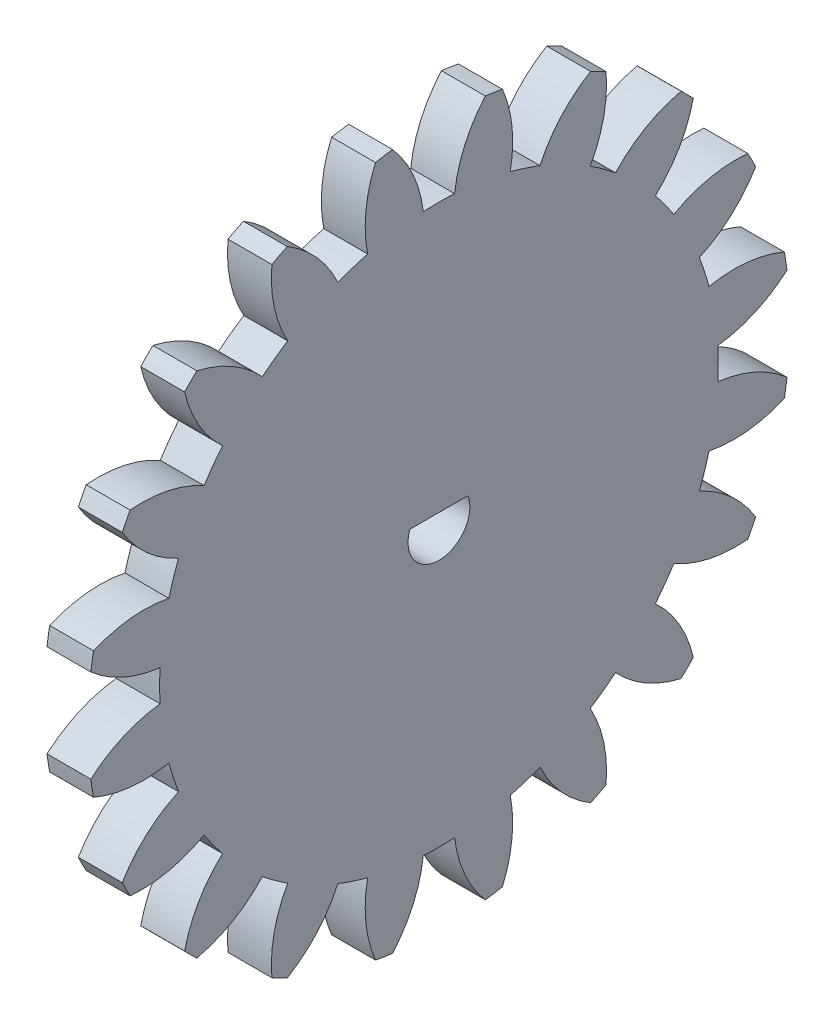
SolidWorks part; units mm, degrees
ref_plane "Plane1" through (0, 0, 0) normal (0, 0, 1) x (1, 0, 0)
ref_plane "Plane2" through (0, 0, 0) normal (0, 1, 0) x (1, 0, 0)
ref_plane "Plane3" through (0, 0, 0) normal (1, 0, 0) x (0, 0, -1)
sketch "HoldingSke" plane through (0, 0, 0) normal (0, 1, 0) x (1, 0, 0)
  line L0 (0, 0) -> (0.2349, -0.0855)
  line L1 (-15, 0) -> (100, 0) construction
  line L2 (0, 0) -> (-2.1039, 2.3779)
  line L3 (0, 0) -> (-11.863, 4.5341)
  line L4 (0, 0) -> (8.1152, 2.9537)
  line L5 (0, 0) -> (-46.8476, -17.4728)
  line L6 (0, 0) -> (-4.5593, -3.0762)
  line L7 (-2.1039, 2.3779) -> (8.6586, 51.2059)
  line L8 (-76.2, 54.61) -> (-76.1, 54.61)
  line L9 (-71.009, 38.7566) -> (-53.1078, 45.2721)
  line L10 (-76.2, 71.12) -> (104.1128, 71.12)
  line L11 (0, 0) -> (-5.5, 0)
  line L12 (-76.2, 101.6) -> (-76.073, 101.6)
  line L13 (24.9733, 27.94) -> (52.9518, 28.4284)
  line L14 (24.9733, 27.94) -> (24.9743, 27.94)
  line L15 (24.9733, 27.94) -> (100.4006, 29.5858)
  line L16 (-63.627, -4) -> (-12.827, -4)
  circle A0 centre (0, 0) radius 0.5
  circle A1 centre (0, 0) radius 34.999
  circle A2 centre (0, 0) radius 37.5
  circle A3 centre (0, 0) radius 0.5
  dimension "MHD" = 69.998
  dimension "Hub_dia" = 75
  dimension "Bore" = 1
  dimension "MBD" = 1
  dimension "Num_teeth" = 20
  dimension "Pitch" = 0.25
  dimension "Overall_len" = 50
  dimension "Show_teeth" = 20
  dimension "Thickness" = 5.5
  dimension "OAL" = 50.0001
  dimension "T_dim" = 0.1
  dimension "Ap" = 20
  dimension "H" = 19.05
  dimension "Pitch_radius" = 180.3128
  dimension "Width" = 5.5
  dimension "Backlash" = 0.127
  dimension "Addendum_fac" = 1
  dimension "Dedendum_fac" = 1.25
  dimension "Clearance_fac" = 0.25
  dimension "Dedendum_add" = 0.001
  dimension "Module" = 4
sketch "BasProSke" plane through (0, 0, 0) normal (0, 1, 0) x (1, 0, 0)
  line L0 (-10, 0) -> (60, 0) construction
  line L1 (0, 0) -> (0, 44)
  line L2 (0, 0) -> (5.5, 0)
  line L3 (5.5, 0) -> (5.5, 44)
  line L4 (5.5, 44) -> (0, 44)
  dimension "Thickness" = 5.5
  dimension "Diameter" = 88
revolve "Base-Revolve" add sketch "BasProSke" angle 360 about L0
sketch "TooCutSke" plane through (0, 0, 0) normal (1, 0, 0) x (0, 0, -1)
  line L1 (0, 0) -> (0, 107) construction
  line L2 (0, 0) -> (-3.3605, 39.8586) construction
  line L3 (0, 0) -> (-12.4815, 78.8048) construction
  line L4 (-3.3605, 39.8586) -> (-6.2407, 39.4024) construction
  arc A0 (1.9617, 34.944) -> (-1.9617, 34.944) centre (0, 0) ccw
  arc A1 (5.8321, 43.6374) -> (-5.8321, 43.6374) centre (0, 0) ccw
  circle A2 centre (0, 0) radius 40 construction
  circle A3 centre (0, 0) radius 37.5877 construction
  arc A4 (-1.9617, 34.944) -> (-5.8321, 43.6374) centre (-17.8525, 33.0775) ccw
  arc A5 (5.8321, 43.6374) -> (1.9617, 34.944) centre (17.8525, 33.0775) ccw
  dimension "Root_dia" = 69.998
  dimension "Overcut_dia" = 88.0508
  dimension "Pitch_dia" = 80
  dimension "Base_dia" = 75.1754
  dimension "Flank_rad" = 16
  dimension "Half_ang" = 9
  dimension "Half_CT" = 2.9161
extrude "ToothCut" cut sketch "TooCutSke" along normal through all
fillet "Breaks" [suppressed] radius 0.08 tangent propagation no
fillet "RootFillets" [suppressed] radius 1.001
pattern_circular "TeethCuts" count 20 every 18 about axis through (-10, 0, 0) along (1, 0, 0) of "ToothCut", "RootFillets", "Breaks"
sketch "HubNeaOneSke" plane through (0, 0, 0) normal (-1, 0, 0) x (0, 0, 1)
  circle A0 centre (0, 0) radius 34.999
  dimension "Diameter" = 69.998
extrude "HubNearOne" [suppressed] add sketch "HubNeaOneSke" along normal blind 44.5001
sketch "HubNeaBotSke" plane through (0, 0, 0) normal (-1, 0, 0) x (0, 0, 1)
  circle A0 centre (0, 0) radius 34.999
  dimension "Diameter" = 69.998
extrude "HubNearBoth" [suppressed] add sketch "HubNeaBotSke" along normal blind 22.25
ref_plane "FarPln" through (5.5, 0, 0) normal (1, 0, 0) x (0, 0, -1)
sketch "HubFarSke" plane through (5.5, 0, 0) normal (1, 0, 0) x (0, 0, -1)
  circle A0 centre (0, 0) radius 34.999
  dimension "Diameter" = 69.998
extrude "HubFar" [suppressed] add sketch "HubFarSke" along normal blind 22.25
sketch "BorSke" plane through (0, 0, 0) normal (1, 0, 0) x (0, 0, -1)
  circle A0 centre (0, 0) radius 0.5
  dimension "Diameter" = 1
extrude "Bore" cut sketch "BorSke" along normal mid plane 100.0001
sketch "KeySke" plane through (0, 0, 0) normal (1, 0, 0) x (0, 0, -1)
  line L0 (-0.05, 0) -> (-0.05, 0.6)
  line L1 (-0.05, 0.6) -> (0.05, 0.6)
  line L2 (0.05, 0.6) -> (0.05, 0)
  line L3 (0, 0) -> (0, 34) construction
  line L4 (-0.05, 0) -> (0.05, 0)
  dimension "Offset" = 0.6
  dimension "Width" = 0.1
extrude "Keyway" [suppressed] cut sketch "KeySke" along normal mid plane 100.0001
pattern_circular "Keyway2" [suppressed] count 2 every 90 about axis through (-10, 0, 0) along (1, 0, 0)
sketch "Croquis1" plane through (5.5, 0, 0) normal (1, 0, 0) x (0, 0, -1)
  line L1 (0, -3.875) -> (0, 1.325) construction
  line L2 (0, 1.325) -> (3.6414, 1.325)
  line L3 (0, 1.325) -> (-3.6414, 1.325)
  arc A0 (-3.875, 0) -> (3.875, 0) centre (0, 0) ccw
  arc A1 (3.875, 0) -> (3.6414, 1.325) centre (0, 0) ccw
  arc A2 (-3.6414, 1.325) -> (-3.875, 0) centre (0, 0) ccw
  dimension "D1" = 7.75
  dimension "D2" = 5.2
extrude "Cortar-Extruir1" cut sketch "Croquis1" against normal blind 5.5
sketch "Croquis2" plane through (5.5, 0, 0) normal (1, 0, 0) x (0, 0, -1)
  line L0 (-0.5, 0) -> (0.5, 0)
  arc A0 (0.5, 0) -> (-0.5, 0) centre (0, 0) ccw
extrude "Saliente-Extruir1" [suppressed] add sketch "Croquis2" against normal blind 5.5
equation "' \"Module@HoldingSke\" = 6.35"
equation "' \"Num_teeth@HoldingSke\" = 12"
equation "' \"Ap@HoldingSke\" =  20"
equation "' \"Ap@HoldingSke\" = 20"
equation "' \"Width@HoldingSke\" = 0.5 * 25.4"
equation "' \"Hub_dia@HoldingSke\"= 1 * 25.4"
equation "' \"Hub_dia@HoldingSke\" = 1 * 25.4"
equation "' \"Overall_len@HoldingSke\" = 1.0 * 25.4"
equation "' \"Bore@HoldingSke\" = 0.75 * 25.4"
equation "' \"T_dim@HoldingSke\" = 0.1 * 25.4"
equation "' \"Width@KeySke\" = 0.25 * 25.4"
equation "' \"Show_teeth@HoldingSke\" = 13"
equation "' \"Backlash@HoldingSke\" = 0.009 * 25.4"
equation "' \"Addendum_fac@HoldingSke\" = 1.0"
equation "' \"Dedendum_fac@HoldingSke\" = 1.25"
equation "' \"Dedendum_add@HoldingSke\" = 0.00005 * 25.4"
equation "' \"Clearance_fac@HoldingSke\" = 0.25"
equation "\"Pitch@HoldingSke\" = 1 / \"Module@HoldingSke\""
equation "\"Overcut_dia@TooCutSke\" = (\"Num_teeth@HoldingSke\" + 2 * \"Addendum_fac@HoldingSke\") / \"Pitch@HoldingSke\" + 0.002 * 25.4"
equation "\"Pitch_dia@TooCutSke\" = \"Num_teeth@HoldingSke\" / \"Pitch@HoldingSke\""
equation "\"Base_dia@TooCutSke\" = \"Num_teeth@HoldingSke\" / \"Pitch@HoldingSke\" * cos((\"Ap@HoldingSke\"  * 3.14159265 / 180))"
equation "\"Root_dia@TooCutSke\" = (\"Num_teeth@HoldingSke\" + 2) / \"Pitch@HoldingSke\" - 2 * (\"Addendum_fac@HoldingSke\" + \"Dedendum_fac@HoldingSke\") / \"Pitch@HoldingSke\" - \"Dedendum_add@HoldingSke\" * 2"
equation "\"Half_ang@TooCutSke\" = 180 / \"Num_teeth@HoldingSke\""
equation "\"Half_CT@TooCutSke\" = \"Num_teeth@HoldingSke\" / \"Pitch@HoldingSke\" * sin((3.14159265 / 2 / \"Num_teeth@HoldingSke\")) / 2 - 7 * \"Backlash@HoldingSke\" / 4"
equation "\"Flank_rad@TooCutSke\" = \"Num_teeth@HoldingSke\" / \"Pitch@HoldingSke\" / 5"
equation "\"Radius@RootFillets\" = \"Clearance_fac@HoldingSke\" / \"Pitch@HoldingSke\" + \"Dedendum_add@HoldingSke\""
equation "\"Break_rad@Breaks\" = 0.02 / \"Pitch@HoldingSke\""
equation "\"Thickness@HoldingSke\" = \"Width@HoldingSke\""
equation "\"OAL@HoldingSke\" = \"Thickness@HoldingSke\""
equation "\"MHD@HoldingSke\" = (\"Num_teeth@HoldingSke\" + 2) / \"Pitch@HoldingSke\" - 2 * (\"Addendum_fac@HoldingSke\" + \"Dedendum_fac@HoldingSke\")  / \"Pitch@HoldingSke\" - \"Dedendum_add@HoldingSke\" * 2"
equation "\"MBD@HoldingSke\" = (\"Num_teeth@HoldingSke\" + 2) / \"Pitch@HoldingSke\" - 2 * (\"Addendum_fac@HoldingSke\" + \"Dedendum_fac@HoldingSke\")  / \"Pitch@HoldingSke\" - \"Dedendum_add@HoldingSke\" * 2 - 0.002 * 25.4"
equation "\"MHD@HoldingSke\" = ((sgn( \"MHD@HoldingSke\" - \"Hub_dia@HoldingSke\" )-1)*( \"MHD@HoldingSke\" - \"Hub_dia@HoldingSke\" ))/-2+ \"Hub_dia@HoldingSke\""
equation "\"MBD@HoldingSke\" = ((sgn( \"MBD@HoldingSke\" - \"Bore@HoldingSke\" )-1)*( \"MBD@HoldingSke\" - \"Bore@HoldingSke\" ))/-2+ \"Bore@HoldingSke\""
equation "\"OAL@HoldingSke\" = ((sgn( \"OAL@HoldingSke\" - \"Overall_len@HoldingSke\" )+1)*( \"OAL@HoldingSke\" - \"Overall_len@HoldingSke\" ))/2 + \"Overall_len@HoldingSke\" + 0.000002 * 25.4"
equation "\"Num_teeth@TeethCuts\" = int( \"Show_teeth@HoldingSke\" ) + 1"
equation "\"Num_teeth@TeethCuts\" = ((sgn( \"Num_teeth@TeethCuts\" - \"Num_teeth@HoldingSke\" )-1)*( \"Num_teeth@TeethCuts\" - \"Num_teeth@HoldingSke\" ))/-2+ \"Num_teeth@HoldingSke\""
equation "\"Num_teeth@TeethCuts\" = ((sgn( \"Num_teeth@TeethCuts\" - 2.0)+1)*( \"Num_teeth@TeethCuts\" - 2.0))/2 +2.0"
equation "\"Angle@TeethCuts\" = 360.0 / \"Num_teeth@HoldingSke\""
equation "\"Diameter@BasProSke\" = (\"Num_teeth@HoldingSke\" + 2 * \"Addendum_fac@HoldingSke\") / \"Pitch@HoldingSke\""
equation "\"Thickness@BasProSke\"  = \"Thickness@HoldingSke\""
equation "' \"Fillet_rad@BasProSke\" =  \"Thickness@HoldingSke\" * 0.05"
equation "' \"Fillet_rad@BasProSke\" = \"Thickness@HoldingSke\" * 0.05"
equation "\"MHD@HoldingSke\" = ((sgn( \"MHD@HoldingSke\" - \"Root_dia@TooCutSke\" )-1)*( \"MHD@HoldingSke\" - \"Root_dia@TooCutSke\" ))/-2+ \"Root_dia@TooCutSke\""
equation "\"Diameter@HubNeaOneSke\" = \"MHD@HoldingSke\""
equation "\"Length@HubNearOne\" = \"OAL@HoldingSke\" - \"Thickness@BasProSke\""
equation "\"Diameter@HubNeaBotSke\" = \"MHD@HoldingSke\""
equation "\"Length@HubNearBoth\" = ( \"OAL@HoldingSke\" - \"Thickness@BasProSke\" ) / 2.0"
equation "\"Thickness@FarPln\" = \"Thickness@BasProSke\""
equation "\"Diameter@HubFarSke\" = \"MHD@HoldingSke\""
equation "\"Length@HubFar\" = ( \"OAL@HoldingSke\" - \"Thickness@BasProSke\" ) / 2.0"
equation "\"Diameter@BorSke\" = \"MBD@HoldingSke\""
equation "\"D1@Bore\" = \"OAL@HoldingSke\" * 2.0"
equation "\"D1@Keyway\" = \"OAL@HoldingSke\" * 2.0"
equation "\"Offset@KeySke\" = \"T_dim@HoldingSke\" + \"MBD@HoldingSke\" / 2.0"
